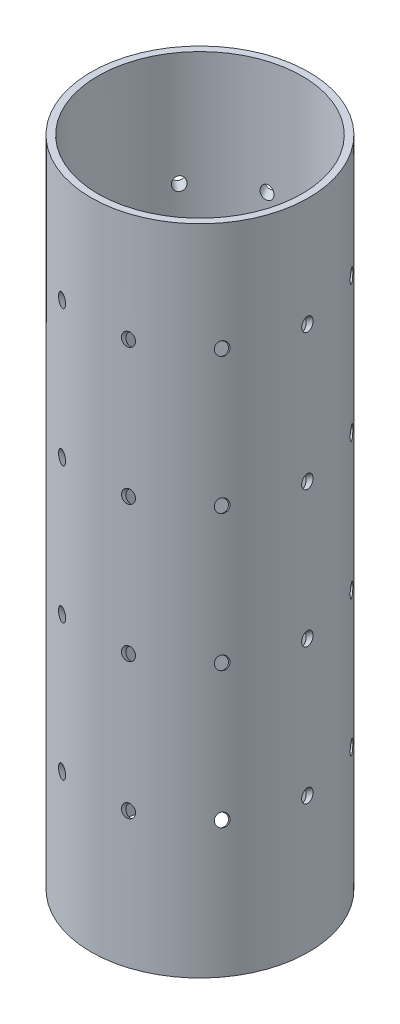
SolidWorks part; units mm, degrees
ref_plane "Front" through (0, 0, 0) normal (0, 0, 1) x (1, 0, 0)
ref_plane "Top" through (0, 0, 0) normal (0, 1, 0) x (1, 0, 0)
ref_plane "Right" through (0, 0, 0) normal (1, 0, 0) x (0, 0, -1)
sketch "Sketch1" plane through (0, 0, 0) normal (0, 1, 0) x (1, 0, 0)
  circle A0 centre (0, 0) radius 47.625
  circle A1 centre (0, 0) radius 50.8
  dimension "D1" = 95.25
  dimension "D2" = 3.175
extrude "Boss-Extrude1" add sketch "Sketch1" along normal blind 304.8
sketch "Sketch2" plane through (0, 0, 0) normal (0, 0, 1) x (1, 0, 0)
  line L0 (50.8, 254) -> (61.2032, 261.2844)
  line L1 (50.8, 0) -> (50.8, 304.8) construction
  line L2 (50.8, 254) -> (40.3968, 246.7156)
  line L3 (50.8, 254) -> (113.5408, 254) construction
  line L4 (50.8, 304.8) -> (-50.8, 304.8) construction
  point P4 (0, 0)
  point P7 (0, 0)
  dimension "D1" = 35
  dimension "D2" = 25.4
  dimension "D3" = 50.8
ref_plane "Plane2" through (61.2032, 261.2844, 0) normal (0.8192, 0.5736, 0) x (0, 0, -1)
sketch "Sketch4" plane through (61.2032, 261.2844, 0) normal (0.8192, 0.5736, 0) x (0, 0, -1)
  circle A0 centre (-0.6144, 0) radius 2.6162
  dimension "D1" = 5.2324
extrude "Cut-Extrude1" cut sketch "Sketch4" against normal up to next
pattern_circular "CirPattern1" count 10 over 360 about axis through (0, 304.8, 0) along (0, 1, 0) of "Cut-Extrude1"
pattern_linear "LPattern2" count 4 spacing 63.5 along (0, -1, 0) of "CirPattern1"
